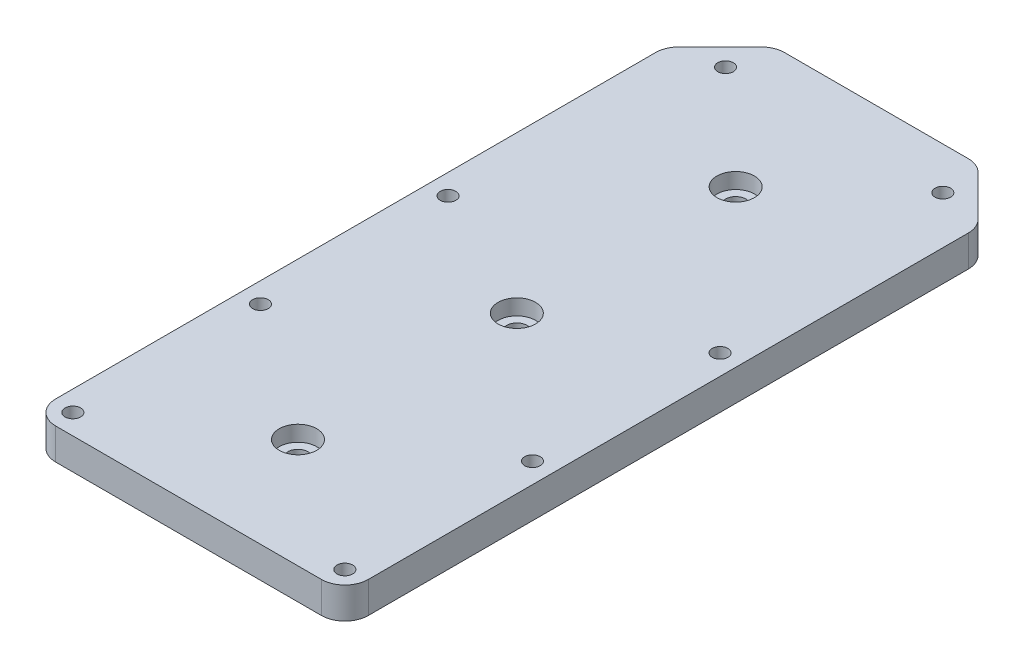
SolidWorks part; units mm, degrees
ref_plane "Front Plane" through (0, 0, 0) normal (0, 0, 1) x (1, 0, 0)
ref_plane "Top Plane" through (0, 0, 0) normal (0, 1, 0) x (1, 0, 0)
ref_plane "Right Plane" through (0, 0, 0) normal (1, 0, 0) x (0, 0, -1)
sketch "Sketch1" plane through (0, 0, 0) normal (0, 1, 0) x (1, 0, 0)
  line L2 (-42.5743, 39.6947) -> (-42.5743, -162.8053)
  line L3 (-42.5743, -162.8053) -> (57.4257, -162.8053)
  line L4 (57.4257, 39.6947) -> (57.4257, -162.8053)
  line L14 (-25.0743, 57.1947) -> (39.9257, 57.1947)
  line L17 (-25.0743, 57.1947) -> (39.9257, 57.1947)
  line L19 (-25.0743, 57.1947) -> (-42.5743, 39.6947)
  line L20 (39.9257, 57.1947) -> (57.4257, 39.6947)
  circle A1 centre (7.4257, 12.1947) radius 3.25
  circle A2 centre (7.4257, -57.8053) radius 3.25
  circle A3 centre (7.4257, -127.8053) radius 3.25
  circle A4 centre (-36.0743, -156.3053) radius 2.5
  circle A5 centre (50.9257, -156.3053) radius 2.5
  circle A6 centre (-36.0743, -96.3053) radius 2.5
  circle A7 centre (50.9257, -96.3053) radius 2.5
  circle A8 centre (-36.0743, -36.3053) radius 2.5
  circle A9 centre (50.9257, -36.3053) radius 2.5
  circle A10 centre (-27.3243, 43.6947) radius 2.5
  circle A11 centre (42.1757, 43.6947) radius 2.5
  point P15 (7.4257, -156.3053)
  point P32 (7.4257, 43.6947)
  point P39 (7.4257, 57.1947)
  dimension "D5" = 6.5
  dimension "D6" = 6.5
  dimension "D7" = 6.5
  dimension "D9" = 5
  dimension "D10" = 5
  dimension "D14" = 5
  dimension "D15" = 5
  dimension "D3" = 60
  dimension "D4" = 70
  dimension "D8" = 87
  dimension "D11" = 60
  dimension "D13" = 69.5
  dimension "D17" = 65
extrude "Boss-Extrude1" add sketch "Sketch1" along normal blind 10 contours L20 L14 L19 L2 L3 L4 A11 A10 A9 A8 A7 A6 A5 A4 A3 A2 A1 region at (7.4257, 0, 54.2079)
sketch "Sketch2" plane through (0, 10, 0) normal (0, 1, 0) x (1, 0, 0)
  circle A1 centre (7.4257, 12.1947) radius 6
  circle A2 centre (7.4257, -57.8053) radius 6
  circle A3 centre (7.4257, -127.8053) radius 6
  dimension "D1" = 12
  dimension "D2" = 12
  dimension "D3" = 12
extrude "Cut-Extrude1" cut sketch "Sketch2" against normal blind 5
fillet "Fillet1" radius 7.5 6 edges at (57.4257, 5, 162.8053) (-42.5743, 5, 162.8053) (-42.5743, 5, -39.6947) (-25.0743, 5, -57.1947) (57.4257, 5, -39.6947) (39.9257, 5, -57.1947)
